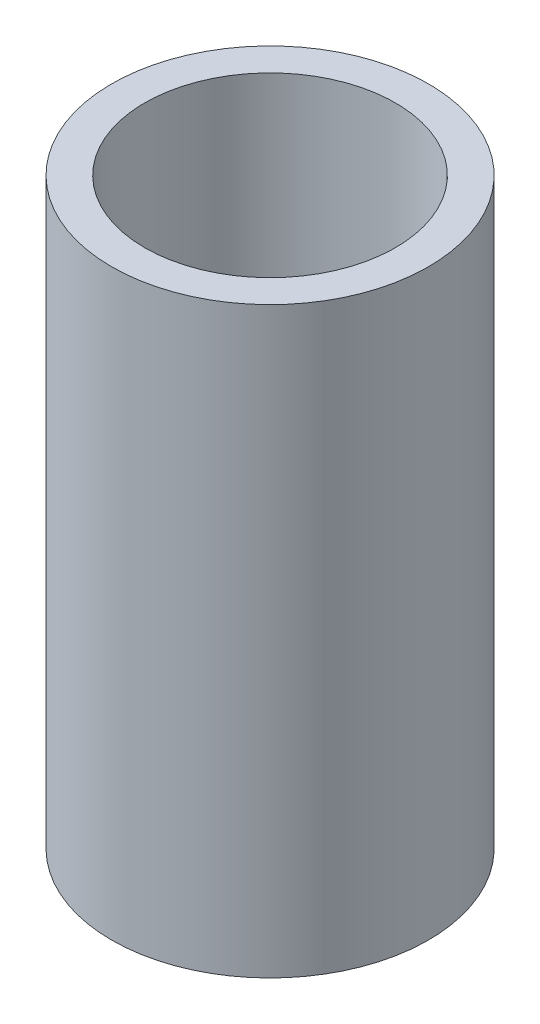
SolidWorks part; units mm, degrees
ref_plane "Front Plane" through (0, 0, 0) normal (0, 0, 1) x (1, 0, 0)
ref_plane "Top Plane" through (0, 0, 0) normal (0, 1, 0) x (1, 0, 0)
ref_plane "Right Plane" through (0, 0, 0) normal (1, 0, 0) x (0, 0, -1)
sketch "Sketch1" plane through (0, 0, 0) normal (0, 1, 0) x (1, 0, 0)
  circle A0 centre (0, 0) radius 20
  dimension "SLEEVE_OD" = 40
extrude "Boss-Extrude1" add sketch "Sketch1" along normal blind 73.6157
sketch "Sketch2" plane through (0, 0, 0) normal (0, 1, 0) x (1, 0, 0)
  circle A0 centre (0, 0) radius 15.8329
  dimension "BORE_D" = 31.6657
extrude "Cut-Extrude1" cut sketch "Sketch2" along normal through all
chamfer "Chamfer1" distance 3.7284 angle 30 rebuild error yes
